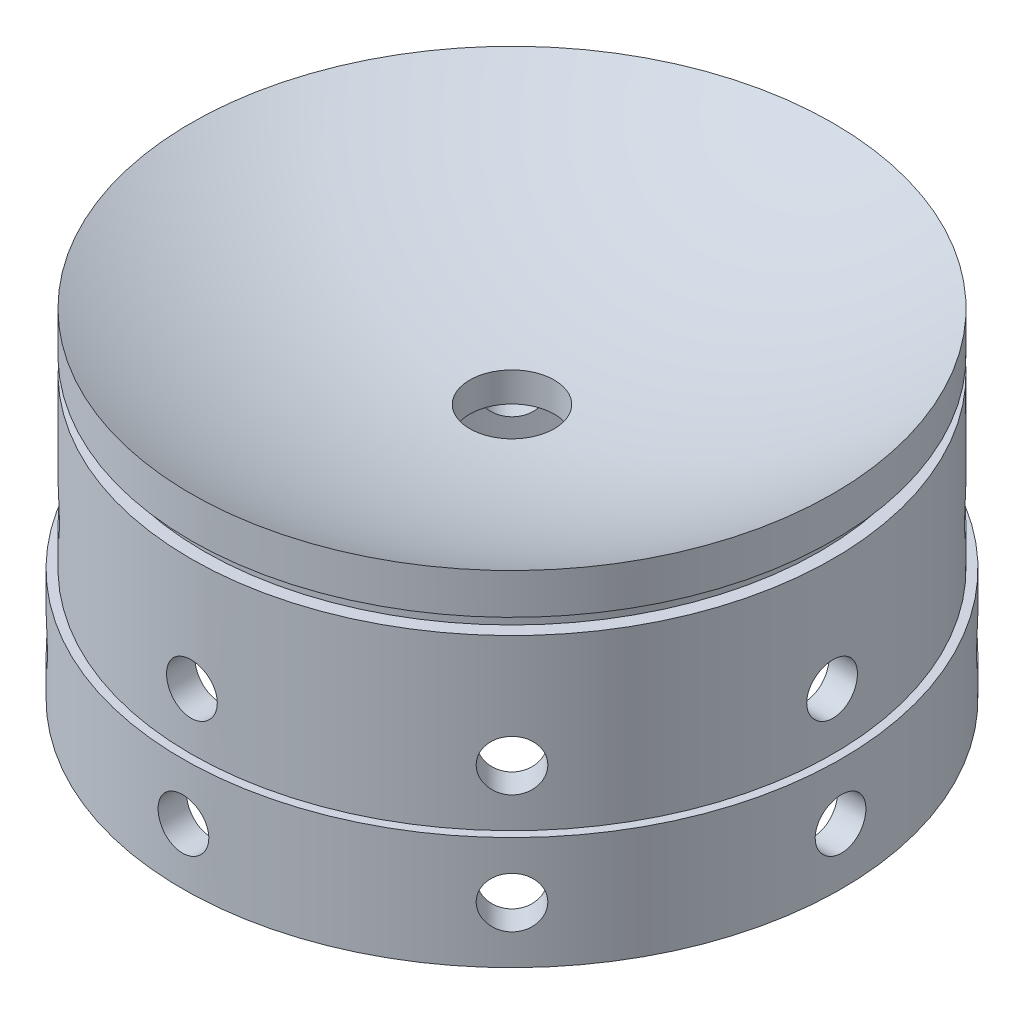
SolidWorks part; units mm, degrees
ref_plane "Front Plane" through (0, 0, 0) normal (0, 0, 1) x (1, 0, 0)
ref_plane "Top Plane" through (0, 0, 0) normal (0, 1, 0) x (1, 0, 0)
ref_plane "Right Plane" through (0, 0, 0) normal (1, 0, 0) x (0, 0, -1)
sketch "Sketch1" plane through (0, 0, 0) normal (0, 0, 1) x (1, 0, 0)
  line L0 (0, 0) -> (0, 6.35)
  line L1 (0, 0) -> (72.39, 0)
  line L2 (72.39, 0) -> (72.39, 12.7)
  line L3 (72.39, 12.7) -> (69.469, 12.7)
  line L4 (69.469, 12.7) -> (69.469, 16.256)
  line L5 (69.469, 16.256) -> (72.39, 16.256)
  line L6 (72.39, 16.256) -> (72.39, 25.4)
  line L9 (72.39, 6.35) -> (0, 6.35) construction
  line L10 (72.39, 0) -> (72.39, -25.4)
  line L11 (72.39, -25.4) -> (66.04, -25.4)
  line L12 (66.04, -25.4) -> (66.04, 0)
  line L13 (74.93, 68.1653) -> (74.93, 53.6699) construction
  line L14 (67.945, -50.8) -> (67.945, -25.4)
  line L15 (67.945, -50.8) -> (74.295, -50.8)
  line L16 (9.525, 6.6588) -> (9.525, 0)
  line L17 (73.025, 45.3691) -> (73.025, 21.7883) construction
  line L18 (74.295, -50.8) -> (74.295, -25.4)
  line L19 (74.295, -25.4) -> (72.39, -25.4)
  arc A0 (72.39, 25.4) -> (0, 6.35) centre (0, 153.416) cw
  dimension "D1" = 72.39
  dimension "D9" = 6.35
  dimension "D12" = 9.525
  dimension "D3" = 12.7
  dimension "D4" = 3.556
  dimension "D2" = 73.025
  dimension "D13" = 3.556
  dimension "D6" = 6.35
  dimension "D7" = 25.4
  dimension "D8" = 74.93
  dimension "D10" = 25.4
  dimension "D11" = 74.295
  dimension "D5" = 25.4
revolve "Revolve1" add sketch "Sketch1" angle 360 about L0 region at (47.8949, 7.7537, 0) region at (69.215, -12.7, 0) region at (71.12, -38.1, 0)
hole_wizard "1/2 (0.45) Diameter Hole3" positions "3DSketch5" profile "Sketch8" hole size "1/2" standard "ANSI Inch"
sketch3d "3DSketch5"
  line L0 (0, -25.4, 0) -> (0, 0, 0) construction
  line L2 (0, -12.7, 0) -> (72.39, -12.7, 0)
  circle A8 centre (0, -25.4, 0) radius 72.39 construction
  circle A9 centre (0, -25.4, 0) radius 72.39
  point P0 (72.39, -12.7, 0)
  point P41 (0, -97.79, 0)
  point P43 (0, -97.79, 0)
  point P53 (72.39, -12.7, 0)
sketch "Sketch8" plane through (72.39, -12.7, 0) normal (0, 1, 0) x (0, 0, -1)
  line L0 (0, 0) -> (0, 75.8229)
  line L1 (0, 75.8229) -> (5.715, 72.389)
  line L2 (5.715, 72.389) -> (5.715, 0)
  line L5 (5.715, 0) -> (0, 0)
  line L10 (0, 75.8229) -> (-5.715, 72.389) construction
  line L11 (0, -6.35) -> (0, 107.95) construction
  dimension "Hole Dia." = 11.43
  dimension "Hole Depth" = 72.389
  dimension "Drill Angle" = 118
hole_wizard "1/2 (0.45) Diameter Hole2" positions "3DSketch6" profile "Sketch9" hole size "1/2" standard "ANSI Inch"
sketch3d "3DSketch6"
  line L0 (0, -25.4, 0) -> (0, -50.8, 0)
  line L2 (0, -38.1, 0) -> (74.295, -38.1, 0)
  circle A0 centre (0, -50.8, 0) radius 74.295 construction
  circle A1 centre (0, -25.4, 0) radius 74.295 construction
  circle A2 centre (0, -50.8, 0) radius 74.295
  circle A3 centre (0, -25.4, 0) radius 74.295
  point P0 (74.295, -38.1, 0)
  point P5 (0, -125.095, 0)
  point P8 (0, -99.695, 0)
  point P10 (0, -125.095, 0)
  point P12 (0, -99.695, 0)
sketch "Sketch9" plane through (74.295, -38.1, 0) normal (0, 1, 0) x (0, 0, -1)
  line L0 (0, 0) -> (0, 77.7279)
  line L1 (0, 77.7279) -> (5.715, 74.294)
  line L2 (5.715, 74.294) -> (5.715, 0)
  line L5 (5.715, 0) -> (0, 0)
  line L10 (0, 77.7279) -> (-5.715, 74.294) construction
  line L11 (0, -6.35) -> (0, 107.95) construction
  dimension "Hole Dia." = 11.43
  dimension "Hole Depth" = 74.294
  dimension "Drill Angle" = 118
ref_axis "CenterAxis" through (0, 6.6588, 0) along (0, -1, 0)
chamfer "Chamfer1" distance 2.54 angle 45 1 edges at (0, -25.4, -67.945)
pattern_circular "CirPattern1" count 8 over 360 about axis through (0, -25.4, 0) along (0, -1, 0) of "1/2 (0.45) Diameter Hole3", "1/2 (0.45) Diameter Hole2"
equation "\"D1@Sketch1\"=(5.75/2)-(0.025in)"
equation "\"D12@Sketch1\"=0.75/2"
equation "\"D2@Sketch1\"=5.75/2"
equation "\"D8@Sketch1\"=5.9/2"
equation "\"D11@Sketch1\"=5.9/2 - (0.025in)"
